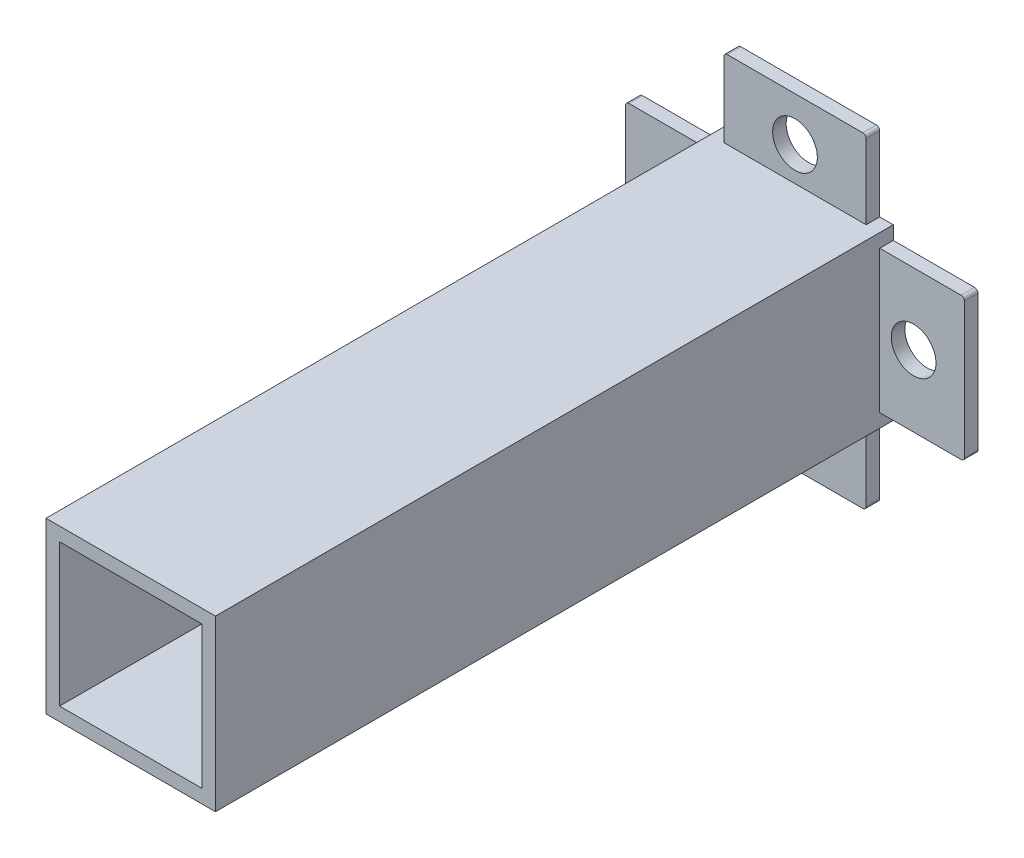
SolidWorks part; units mm, degrees
ref_plane "前视基准面" through (0, 0, 0) normal (0, 0, 1) x (1, 0, 0)
ref_plane "上视基准面" through (0, 0, 0) normal (0, 1, 0) x (1, 0, 0)
ref_plane "右视基准面" through (0, 0, 0) normal (1, 0, 0) x (0, 0, -1)
other "Configuration Table"
sketch "草图1" plane through (0, 0, 0) normal (0, 0, 1) x (1, 0, 0)
  line L0 (0, 0) -> (50, 0)
  line L1 (50, 0) -> (50, -48)
  line L2 (50, -48) -> (0, -48)
  line L3 (0, -48) -> (0, 0)
  dimension "D1" = 50
  dimension "D2" = 48
extrude "凸台-拉伸1" add sketch "草图1" along normal blind 15
sketch "草图2" plane through (0, 0, 15) normal (0, 0, 1) x (1, 0, 0)
  line L0 (50, -24) -> (0, -24)
  line L1 (50, -48) -> (50, 0) construction
  line L2 (0, 0) -> (0, -48) construction
  line L3 (25, 0) -> (25, -48)
  line L4 (50, 0) -> (0, 0) construction
  line L5 (0, -48) -> (50, -48) construction
  line L6 (25, -24) -> (25, -12)
  circle A0 centre (42.5, -6.5) radius 1.9922
  circle A1 centre (42.5, -41.5) radius 1.9922
  circle A2 centre (7.5, -41.5) radius 1.9922
  circle A3 centre (7.5, -6.5) radius 1.9922
  dimension "D1" = 17.5
  dimension "D2" = 17.5
hole_wizard "M5 六角圆柱头螺钉的柱形沉头孔1" positions "草图5" profile "草图4" counterbore size "M5" standard "GB" end condition through all
sketch "草图5" plane through (0, 0, 15) normal (0, 0, 1) x (1, 0, 0)
  point P0 (7.5, -6.5)
  point P3 (42.5, -6.5)
  point P6 (42.5, -41.5)
  point P9 (7.5, -41.5)
sketch "草图4" plane through (7.5, -6.5, 15) normal (1, 0, 0) x (0, -1, 0)
  line L0 (0, 0) -> (0, 15)
  line L1 (0, 15) -> (2.75, 15)
  line L3 (2.75, 15) -> (2.75, 6)
  line L4 (5, 6) -> (2.75, 6)
  line L5 (5, 6) -> (5, 0.025)
  line L6 (5, 0.025) -> (5.025, 0)
  line L7 (5.025, 0) -> (0, 0)
  line L8 (-5, 0.025) -> (-5.025, 0) construction
  line L11 (0, -6.35) -> (0, 107.95) construction
  dimension "通孔孔直径" = 5.5
  dimension "通孔孔深度" = 15
  dimension "柱形沉头孔直径" = 10
  dimension "柱形沉头孔深度" = 6
  dimension "近端锥形沉头孔直径" = 10.05
  dimension "近端锥形沉头孔角度" = 90
fillet "圆角1" radius 1 4 edges at (50, -48, 7.5) (0, -48, 7.5) (0, 0, 7.5) (50, 0, 7.5)
sketch "草图8" plane through (0, 0, 15) normal (0, 0, 1) x (1, 0, 0)
  line L5 (25, -48) -> (25, 0)
  line L6 (1, -48) -> (49, -48) construction
  line L7 (49, 0) -> (1, 0) construction
  line L8 (50, -24) -> (0, -24)
  line L9 (50, -47) -> (50, -1) construction
  line L10 (0, -1) -> (0, -47) construction
  line L11 (25, -24) -> (55, -24)
  line L12 (25, -24) -> (-5, -24)
  circle A0 centre (-5, -24) radius 3.3648
  circle A1 centre (25, -24) radius 3.7667
  circle A2 centre (55, -24) radius 3.2192
  circle A3 centre (40, -24) radius 3.2586
  circle A4 centre (10, -24) radius 3.1199
  dimension "D3" = 15
  dimension "D1" = 30
  dimension "D2" = 60
  dimension "D4" = 15
hole_wizard "M8 六角圆柱头螺钉的柱形沉头孔1" positions "草图9" profile "草图10" counterbore size "M8" standard "GB" end condition through all
sketch "草图9" plane through (0, 0, 0) normal (0, 0, -1) x (-1, 0, 0)
  point P0 (-25, -24)
sketch "草图10" plane through (25, -24, 0) normal (1, 0, 0) x (0, 1, 0)
  line L0 (0, 0) -> (0, 15)
  line L1 (0, 15) -> (4.5, 15)
  line L3 (4.5, 15) -> (4.5, 10)
  line L4 (7.5, 10) -> (4.5, 10)
  line L5 (7.5, 10) -> (7.5, 0.025)
  line L6 (7.5, 0.025) -> (7.525, 0)
  line L7 (7.525, 0) -> (0, 0)
  line L8 (-7.5, 0.025) -> (-7.525, 0) construction
  line L11 (0, -6.35) -> (0, 107.95) construction
  dimension "通孔孔直径" = 9
  dimension "通孔孔深度" = 15
  dimension "柱形沉头孔直径" = 15
  dimension "柱形沉头孔深度" = 10
  dimension "近端锥形沉头孔直径" = 15.05
  dimension "近端锥形沉头孔角度" = 90
sketch "草图11" plane through (0, 0, 15) normal (0, 0, 1) x (1, 0, 0)
  line L0 (12.5, -11.5) -> (36.5, -11.5)
  line L1 (37.5, -11.5) -> (36.5, -11.5)
  line L2 (12.5, -11.5) -> (12.5, -36.5)
  line L3 (14.5, -36.5) -> (14.5, -48)
  line L4 (12.5, -24) -> (12.5, -11.5)
  line L5 (12.5, -11.5) -> (37.5, -11.5)
  line L6 (37.5, -11.5) -> (37.5, -36.5)
  line L7 (37.5, -36.5) -> (12.5, -36.5)
  line L8 (14.5, -13.5) -> (14.5, -34.5)
  line L9 (14.5, -34.5) -> (35.5, -34.5)
  line L10 (35.5, -34.5) -> (35.5, -13.5)
  line L11 (35.5, -13.5) -> (14.5, -13.5)
  line L12 (49, 0) -> (1, 0) construction
  line L13 (25, 0) -> (25, -48)
  line L14 (1, -48) -> (49, -48) construction
  line L15 (50, -24) -> (0, -24)
  line L16 (50, -47) -> (50, -1) construction
  line L17 (0, -1) -> (0, -47) construction
  line L18 (14.5, -48) -> (35.5, -48)
  line L19 (35.5, -48) -> (35.5, -36.5)
  line L20 (12.5, -34.5) -> (0, -34.5)
  line L21 (0, -34.5) -> (0, -13.5)
  line L22 (0, -13.5) -> (12.5, -13.5)
  line L23 (37.5, -34.5) -> (50, -34.5)
  line L24 (50, -34.5) -> (50, -13.5)
  line L25 (50, -13.5) -> (37.5, -13.5)
  line L26 (35.5, -11.5) -> (35.5, 0)
  line L27 (35.5, 0) -> (14.5, 0)
  line L28 (14.5, 0) -> (14.5, -11.5)
  circle A0 centre (7.5, -24) radius 3.3
  circle A1 centre (25, -6.5) radius 3.3
  circle A2 centre (42.5, -24) radius 3.3
  circle A3 centre (25, -41.5) radius 3.3
  point P16 (25, -11.5)
  point P17 (25, -13.5)
  point P24 (37.5, -24)
  point P25 (35.5, -24)
  point P30 (25, -24)
  point P54 (25, -24)
  line M16 (1, -48) -> (49, -48)
  line M18 (50, -47) -> (50, -1)
  line M20 (49, 0) -> (1, 0)
  line M22 (0, -1) -> (0, -47)
  dimension "D5" = 17.5
  dimension "D1" = 25
  dimension "D2" = 21
  dimension "D3" = 25
  dimension "D4" = 21
  dimension "D6" = 4
extrude "凸台-拉伸2" add sketch "草图11" along normal blind 100 contours L15 L8 L11 L13 L5 L0 L2 | L15 L6 L5 L13 L11 L10 | L6 L15 L10 L9 L13 L7 | L8 L15 L2 L7 L13 L9 region at (13.5, -11.6768, 15) region at (30.25, -11.6768, 15) region at (13.5, -24.1768, 15) region at (36.5, -24.1768, 15)
extrude "凸台-拉伸3" add sketch "草图11<3>" along normal blind 2 contours L22 L15 L4 M22 | L20 L2 L15 M22 | L13 L7 L3 M16 | L19 L7 L13 M16 | L6 L23 L15 M18 | L25 L6 L15 M18 | L5 L26 L13 M20 | L28 L5 L13 M20 region at (19.1147, -5.6262, 15) region at (6.0627, -18.1731, 15) region at (30.8853, -5.6262, 15) region at (6.0627, -29.8269, 15) region at (19.1147, -42.3738, 15) region at (43.9373, -18.1731, 15) region at (43.9373, -29.8269, 15) region at (30.8853, -42.3738, 15)
sketch "草图11<3>" plane through (0, 0, 15) normal (0, 0, 1) x (1, 0, 0) same geometry as "草图11"
sketch "草图12" plane through (0, -48, 0) normal (0, -1, 0) x (1, 0, 0)
  line L0 (0, 15) -> (50, 15)
  line L1 (50, 15) -> (50, 0)
  line L2 (50, 0) -> (0, 0)
  line L3 (0, 0) -> (0, 15)
extrude "切除-拉伸1" cut sketch "草图12" against normal through all
fillet "圆角3" radius 0.5 8 edges at (14.5, 0, 16) (0, -13.5, 16) (35.5, 0, 16) (50, -34.5, 16) (50, -13.5, 16) (35.5, -48, 16) (0, -34.5, 16) (14.5, -48, 16)
